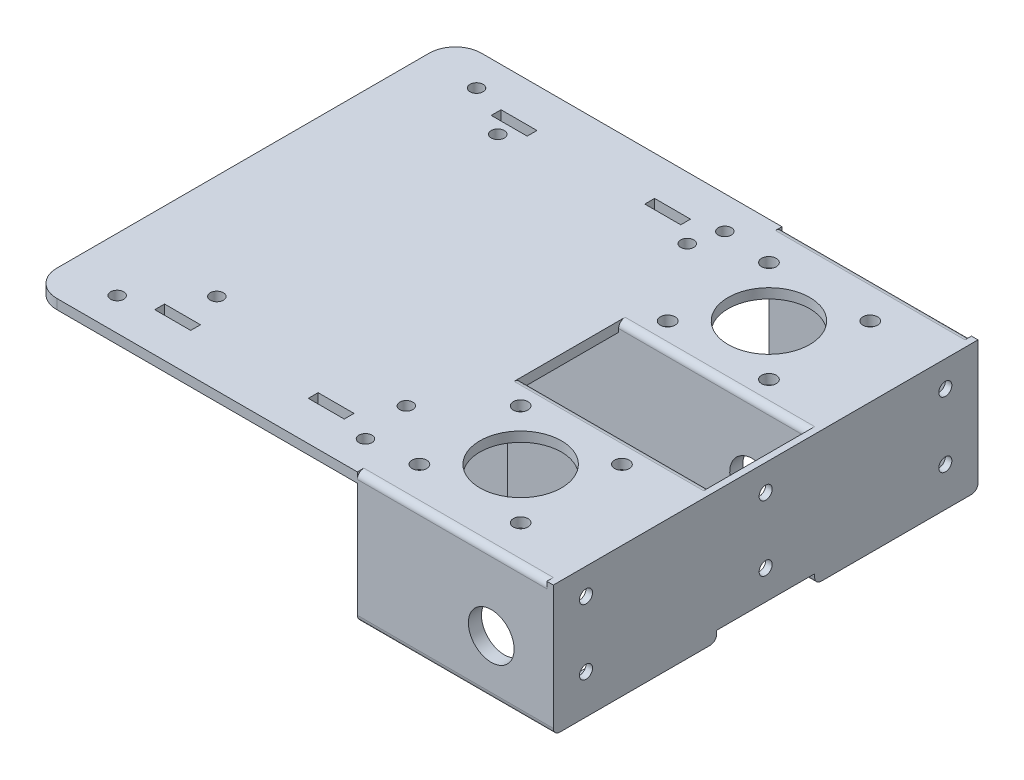
SolidWorks part; units mm, degrees
material "ABS"
ref_plane "前视基准面" through (0, 0, 0) normal (0, 0, 1) x (1, 0, 0)
ref_plane "上视基准面" through (0, 0, 0) normal (0, 1, 0) x (1, 0, 0)
ref_plane "右视基准面" through (0, 0, 0) normal (1, 0, 0) x (0, 0, -1)
sketch "草图1" plane through (0, 0, 0) normal (1, 0, 0) x (0, 0, -1)
  line L1 (4, 5) -> (4, 35)
  line L2 (6, 37) -> (44, 37)
  line L3 (46, 35) -> (46, 5)
  line L5 (50, 2) -> (50, 38)
  line L6 (48, 40) -> (2, 40)
  line L7 (0, 38) -> (0, 2)
  line L8 (48, 0) -> (2, 0)
  line L9 (44, 3) -> (6, 3)
  line L10 (-15, 79.2696) -> (-15, -38.8339) construction
  line L11 (-74, 3) -> (-36, 3)
  line L12 (-78, 0) -> (-32, 0)
  line L13 (-30, 38) -> (-30, 2)
  line L14 (-78, 40) -> (-32, 40)
  line L15 (-80, 2) -> (-80, 38)
  line L16 (-76, 35) -> (-76, 5)
  line L17 (-36, 37) -> (-74, 37)
  line L18 (-34, 5) -> (-34, 35)
  arc A0 (50, 38) -> (48, 40) centre (48, 38) ccw
  arc A1 (44, 37) -> (46, 35) centre (44, 35) cw
  arc A2 (4, 35) -> (6, 37) centre (6, 35) cw
  arc A3 (2, 40) -> (0, 38) centre (2, 38) ccw
  arc A4 (2, 0) -> (0, 2) centre (2, 2) cw
  arc A5 (6, 3) -> (4, 5) centre (6, 5) cw
  arc A6 (44, 3) -> (46, 5) centre (44, 5) ccw
  arc A7 (48, 0) -> (50, 2) centre (48, 2) ccw
  arc A8 (-78, 0) -> (-80, 2) centre (-78, 2) cw
  arc A9 (-74, 3) -> (-76, 5) centre (-74, 5) cw
  arc A10 (-36, 3) -> (-34, 5) centre (-36, 5) ccw
  arc A11 (-32, 0) -> (-30, 2) centre (-32, 2) ccw
  arc A12 (-32, 40) -> (-30, 38) centre (-32, 38) cw
  arc A13 (-34, 35) -> (-36, 37) centre (-36, 35) ccw
  arc A14 (-74, 37) -> (-76, 35) centre (-74, 35) ccw
  arc A15 (-80, 38) -> (-78, 40) centre (-78, 38) cw
  point P11 (50, 40)
  point P18 (0, 40)
  point P21 (0, 0)
  point P28 (50, 0)
  point P55 (-80, 0)
  point P56 (-30, 0)
  point P57 (-30, 40)
  point P58 (-80, 40)
  dimension "D6" = 2
  dimension "D8" = 2
  dimension "D1" = 4
  dimension "D2" = 4
  dimension "D3" = 3
  dimension "D4" = 50
  dimension "D5" = 40
  dimension "D7" = 3
  dimension "D9" = 65
extrude "凸台-拉伸1" add sketch "草图1" along normal blind 60
sketch "草图2" plane through (0, 40, 0) normal (0, 1, 0) x (1, 0, 0)
  line L0 (23, -19.2967) -> (23, 88.9945) construction
  line L1 (-21.8978, 23) -> (76.0197, 23) construction
  line L2 (60, 0) -> (0, 0) construction
  line L3 (0, 48) -> (0, 2) construction
  line L4 (-9.4226, 7.5) -> (65.353, 7.5) construction
  line L5 (7.5, -18.3438) -> (7.5, 73.6232) construction
  line L6 (60, 0) -> (60, -30) construction
  line L7 (60, -15) -> (-8.659, -15) construction
  circle A0 centre (7.5, 7.5) radius 2.25
  circle A1 centre (38.5, 7.5) radius 2.25
  circle A2 centre (38.5, 38.5) radius 2.25
  circle A3 centre (7.5, 38.5) radius 2.25
  circle A4 centre (23, 23) radius 12.5
  circle A5 centre (23, -53) radius 12.5
  circle A6 centre (7.5, -68.5) radius 2.25
  circle A7 centre (38.5, -68.5) radius 2.25
  circle A8 centre (38.5, -37.5) radius 2.25
  circle A9 centre (7.5, -37.5) radius 2.25
  dimension "D5" = 4.5
  dimension "D8" = 25
  dimension "D1" = 23
  dimension "D2" = 23
  dimension "D3" = 15.5
  dimension "D4" = 15.5
  dimension "D6" = 2
  dimension "D7" = 2
extrude "切除-拉伸1" cut sketch "草图2" against normal up to next
sketch "草图3" plane through (0, 0, 0) normal (0, 0, 1) x (1, 0, 0)
  line L0 (23, -15.1885) -> (23, 47.9229) construction
  line L1 (0, 38) -> (0, 2) construction
  line L2 (60, 40) -> (0, 40) construction
  circle A0 centre (41, 17) radius 7
  dimension "D1" = 14
  dimension "D2" = 23
  dimension "D3" = 18
  dimension "D4" = 23
extrude "切除-拉伸2" cut sketch "草图3" against normal through all and the other way through all
sketch "草图6" plane through (0, 40, 0) normal (0, 1, 0) x (1, 0, 0)
  line L0 (60, 50) -> (0, 50) construction
  line L1 (0, 50) -> (-100, 50)
  line L2 (0, 50) -> (0, -80)
  line L3 (0, -80) -> (-100, -80)
  line L4 (-100, 50) -> (-100, -80)
  line L5 (0, -32) -> (0, -78) construction
  point P16 (125, -15)
  dimension "D1" = 100
  dimension "D2" = 130
extrude "凸台-拉伸3" add sketch "草图6" against normal blind 3
sketch "草图9" plane through (0, 40, 0) normal (0, 1, 0) x (1, 0, 0)
  line L0 (-100, -80) -> (0, -80) construction
  line L1 (0, -80) -> (0, -78) construction
  circle A0 centre (-68, 31) radius 2
  circle A1 centre (-68, -55) radius 2
  circle A2 centre (-10, 31) radius 2
  circle A3 centre (-10, -55) radius 2
  dimension "D4" = 4
  dimension "D5" = 4
  dimension "D6" = 4
  dimension "D7" = 4
  dimension "D1" = 86
  dimension "D2" = 86
  dimension "D3" = 58
  dimension "D8" = 25
  dimension "D9" = 10
extrude "切除-拉伸3" cut sketch "草图9" against normal up to next
sketch "草图19" plane through (0, 40, 0) normal (0, 1, 0) x (1, 0, 0)
  line L0 (-100, -15) -> (15.7358, -15) construction
  line L1 (-45.5, -94.6974) -> (-45.5, 61.8979) construction
  line L3 (-100, 50) -> (-100, -80) construction
  line L4 (0, -32) -> (0, 2) construction
  circle A0 centre (-83.5, 40) radius 2
  circle A1 centre (-7.5, 40) radius 2
  circle A2 centre (-7.5, -70) radius 2
  circle A3 centre (-83.5, -70) radius 2
  point P12 (-100, -15)
  dimension "D1" = 4
  dimension "D2" = 110
  dimension "D3" = 76
  dimension "D4" = 7.5
extrude "切除-拉伸7" cut sketch "草图19" against normal up to next and the other way through all
sketch "草图16" plane through (0, 40, 0) normal (0, 1, 0) x (1, 0, 0)
  line L0 (0, 48) -> (0, 50) construction
  line L1 (-27, 38) -> (-16, 38)
  line L2 (-27, 38) -> (-27, 35)
  line L3 (-27, 35) -> (-16, 35)
  line L4 (-16, 38) -> (-16, 35)
  line L5 (0, -32) -> (0, 2) construction
  line L6 (-45, 45.899) -> (-45, -58.675) construction
  line L7 (-74, 38) -> (-74, 35)
  line L8 (-63, 35) -> (-74, 35)
  line L9 (-63, 38) -> (-63, 35)
  line L10 (-63, 38) -> (-74, 38)
  line L11 (0, -15) -> (-76.25, -15) construction
  line L13 (-63, -68) -> (-74, -68)
  line L14 (-63, -68) -> (-63, -65)
  line L15 (-63, -65) -> (-74, -65)
  line L16 (-74, -68) -> (-74, -65)
  line L17 (-16, -68) -> (-16, -65)
  line L18 (-27, -65) -> (-16, -65)
  line L19 (-27, -68) -> (-27, -65)
  line L20 (-27, -68) -> (-16, -68)
  point P6 (0, -15)
  dimension "D1" = 16
  dimension "D2" = 11
  dimension "D3" = 3
  dimension "D5" = 47
  dimension "D6" = 100
extrude "切除-拉伸5" cut sketch "草图16" against normal up to next
sketch "草图13" plane through (0, 0, 0) normal (0, -1, 0) x (1, 0, 0)
  line L0 (0, 15) -> (34.395, 15) construction
  line L1 (5, -44) -> (50, -44)
  line L2 (5, -44) -> (5, -4)
  line L3 (5, -4) -> (50, -4)
  line L4 (50, -44) -> (50, -4)
  line L5 (0, 30) -> (0, 0) construction
  line L6 (50, 74) -> (50, 34)
  line L7 (5, 34) -> (50, 34)
  line L8 (5, 74) -> (5, 34)
  line L9 (5, 74) -> (50, 74)
  line L10 (60, -2) -> (0, -2) construction
  line L11 (0, -2) -> (0, -48) construction
  dimension "D1" = 45
  dimension "D2" = 40
  dimension "D3" = 2
  dimension "D4" = 5
extrude "切除-拉伸4" cut sketch "草图13" against normal up to next
sketch "草图7" plane through (0, 0, 0) normal (-1, 0, 0) x (0, 0, 1)
  line L0 (-2, 0) -> (-48, 0) construction
  line L1 (-2, 0) -> (0, 0)
  line L2 (-2, 0) -> (-2, 37)
  line L3 (-2, 37) -> (0, 37)
  line L4 (0, 0) -> (0, 37)
  line L5 (78, 0) -> (32, 0) construction
  line L6 (30, 37) -> (32, 37)
  line L7 (30, 37) -> (30, 0)
  line L8 (30, 0) -> (32, 0)
  line L9 (32, 37) -> (32, 0)
  dimension "D1" = 2
  dimension "D2" = 2
extrude "凸台-拉伸4" add sketch "草图7" along normal blind 100
sketch "草图8" plane through (0, 0, 0) normal (0, -1, 0) x (1, 0, 0)
  line L1 (-100, -2) -> (-30, -2)
  line L2 (-100, -2) -> (-100, 32)
  line L3 (-100, 32) -> (-30, 32)
  line L4 (-30, -2) -> (-30, 32)
  line L5 (-100, 32) -> (0, 32) construction
  point P5 (-30, 32)
  point P7 (-100, -2)
  dimension "D1" = 70
extrude "凸台-拉伸5" add sketch "草图8" against normal blind 3
fillet "圆角1" radius 8 2 edges at (-100, 38.5, 80) (-100, 38.5, -50)
sketch "草图14" plane through (0, 0, 0) normal (-1, 0, 0) x (0, 0, 1)
  line L0 (15, 0) -> (15, 34.9461) construction
  line L1 (-47, 32) -> (-4, 32)
  line L2 (-47, 32) -> (-47, 37)
  line L3 (-47, 37) -> (-4, 37)
  line L4 (-4, 32) -> (-4, 37)
  line L5 (-2, 0) -> (32, 0) construction
  line L6 (34, 32) -> (34, 37)
  line L7 (77, 37) -> (34, 37)
  line L8 (77, 32) -> (77, 37)
  line L9 (77, 32) -> (34, 32)
  line L10 (-2, 37) -> (-6, 37) construction
  line L11 (-44, 37) -> (-50, 37) construction
  point P13 (-4, 37)
  point P16 (-47, 37)
  dimension "D1" = 5
extrude "凸台-拉伸8" add sketch "草图14" against normal blind 1
sketch "草图17" plane through (0, 0, 0) normal (0, -1, 0) x (1, 0, 0)
  line L0 (-100, 15) -> (-30, 15) construction
  line L1 (-100, -2) -> (-100, 32) construction
  line L2 (-30, 0) -> (-30, 30) construction
  circle A0 centre (-83, 15) radius 1.5
  circle A1 centre (-43, 15) radius 1.5
  dimension "D1" = 3
  dimension "D2" = 3
  dimension "D3" = 40
  dimension "D4" = 13
extrude "切除-拉伸6" cut sketch "草图17" against normal blind 3
sketch "草图18" plane through (60, 0, 0) normal (1, 0, 0) x (0, 0, -1)
  line L1 (-80, 40) -> (50, 40)
  line L2 (-80, 40) -> (-80, 3)
  line L3 (-80, 3) -> (50, 3)
  line L4 (50, 40) -> (50, 3)
  line L8 (50, 2) -> (50, 38) construction
  line L9 (-80, 38) -> (-80, 2) construction
  line L11 (-74, 3) -> (-36, 3) construction
extrude "凸台-拉伸9" add sketch "草图18" against normal blind 2
sketch "草图20" plane through (60, 0, 0) normal (1, 0, 0) x (0, 0, -1)
  line L0 (-80, 22) -> (60.3079, 22) construction
  line L2 (50, 40) -> (-80, 40) construction
  line L3 (-15, 40) -> (-15, -8.6582) construction
  circle A0 centre (-70, 32) radius 2
  circle A1 centre (-70, 12) radius 2
  circle A2 centre (40, 12) radius 2
  circle A3 centre (40, 32) radius 2
  circle A4 centre (-15, 32) radius 2
  circle A5 centre (-15, 12) radius 2
  dimension "D1" = 4
  dimension "D5" = 4
  dimension "D2" = 18
  dimension "D3" = 10
  dimension "D4" = 110
  dimension "D6" = 10
extrude "切除-拉伸8" cut sketch "草图20" against normal up to next
fillet "圆角2" radius 5 4 edges at (-50, 0, 32) (-50, 0, -2) (-65, 3, 30) (-65, 3, 0)
